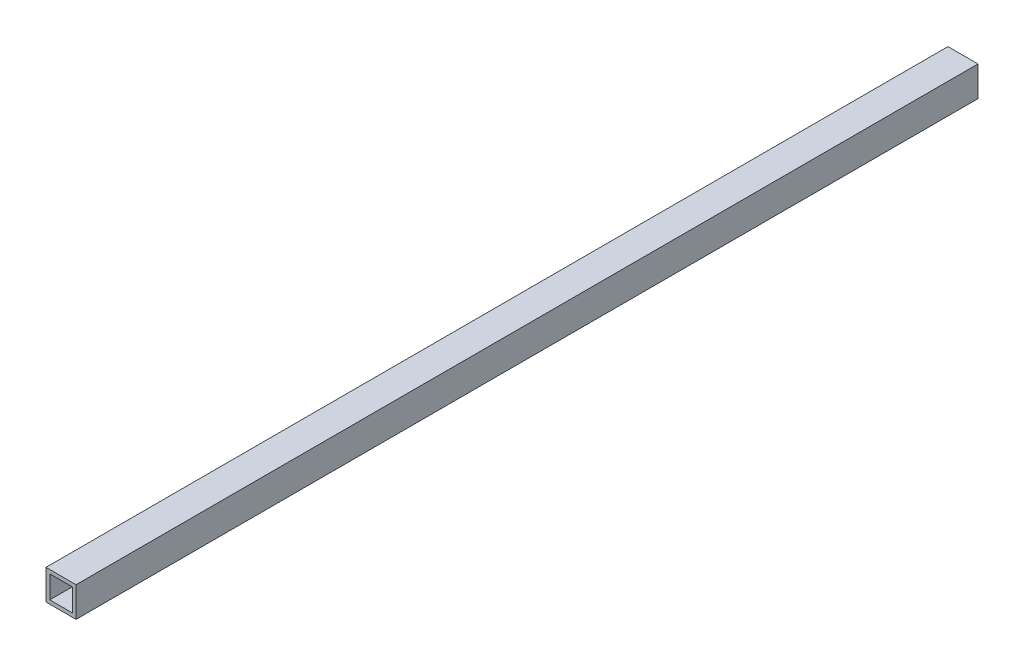
SolidWorks part; units mm, degrees
ref_plane "Front Plane" through (0, 0, 0) normal (0, 0, 1) x (1, 0, 0)
ref_plane "Top Plane" through (0, 0, 0) normal (0, 1, 0) x (1, 0, 0)
ref_plane "Right Plane" through (0, 0, 0) normal (1, 0, 0) x (0, 0, -1)
sketch "Sketch1" plane through (0, 0, 0) normal (0, 0, 1) x (1, 0, 0)
  line L0 (12.7, 0) -> (9.525, 0) construction
  line L1 (-12.7, 0) -> (12.7, 0) construction
  line L2 (0, 12.7) -> (0, -12.7)
  point P7 (0, 0)
sketch "Sketch2" plane through (0, 0, 0) normal (1, 0, 0) x (0, 0, -1)
  line L0 (381, 0) -> (-381, 0)
  point P4 (0, 0)
  dimension "Length" = 762
sketch "Sketch3" plane through (0, 0, 0) normal (0, 0, 1) x (1, 0, 0)
  line L0 (-12.7, 0) -> (12.7, 0) construction
  line L5 (12.7, -12.7) -> (-12.7, -12.7)
  line L6 (12.7, -12.7) -> (12.7, 12.7)
  line L11 (12.7, 12.7) -> (-12.7, 12.7)
  line L12 (-12.7, -12.7) -> (-12.7, 12.7)
  line L14 (12.7, -12.7) -> (-12.7, 12.7) construction
  line L15 (12.7, 12.7) -> (-12.7, -12.7) construction
  line L16 (9.525, -9.525) -> (-9.525, -9.525)
  line L17 (9.525, -9.525) -> (9.525, 9.525)
  line L18 (9.525, 9.525) -> (-9.525, 9.525)
  line L19 (-9.525, -9.525) -> (-9.525, 9.525)
  line L20 (9.525, -9.525) -> (-9.525, 9.525) construction
  line L21 (9.525, 9.525) -> (-9.525, -9.525) construction
  point P0 (0, 0)
  point P5 (0, 0)
  point P13 (9.525, -12.7)
  dimension "D1" = 3.175
extrude "Boss-Extrude1" add sketch "Sketch3" along normal up to vertex (381 mm away) and the other way up to vertex (381 mm away) up to point (0, 0, 381) other way up to point (0, 0, -381)
sketch "Sketch5" plane through (0, 0, 0) normal (1, 0, 0) x (0, 0, -1)
  line L0 (-381, 0) -> (381, 0) construction
  line L3 (-381, -12.7) -> (-381, 12.7) construction
  line L4 (381, -12.7) -> (381, 12.7) construction
  point P6 (-352.425, 0)
  point P7 (-342.9, 0)
  point P8 (342.9, 0)
  point P10 (352.425, 0)
  dimension "D1" = 28.575
  dimension "D2" = 38.1
  dimension "D3" = 28.575
  dimension "D4" = 38.1
equation "\"D1@Sketch3\"=\"Wall thickness@Sketch1\""
equation "\"D1@Sketch5\"=\"Width@Sketch1\"*1.125"
equation "\"D2@Sketch5\"=\"Width@Sketch1\"*1.5"
equation "\"D3@Sketch5\"=\"D1@Sketch5\""
equation "\"D4@Sketch5\"=\"D2@Sketch5\""
equation "\"D2@Sketch3\"=\"Wall Thickness@Sketch1\""
